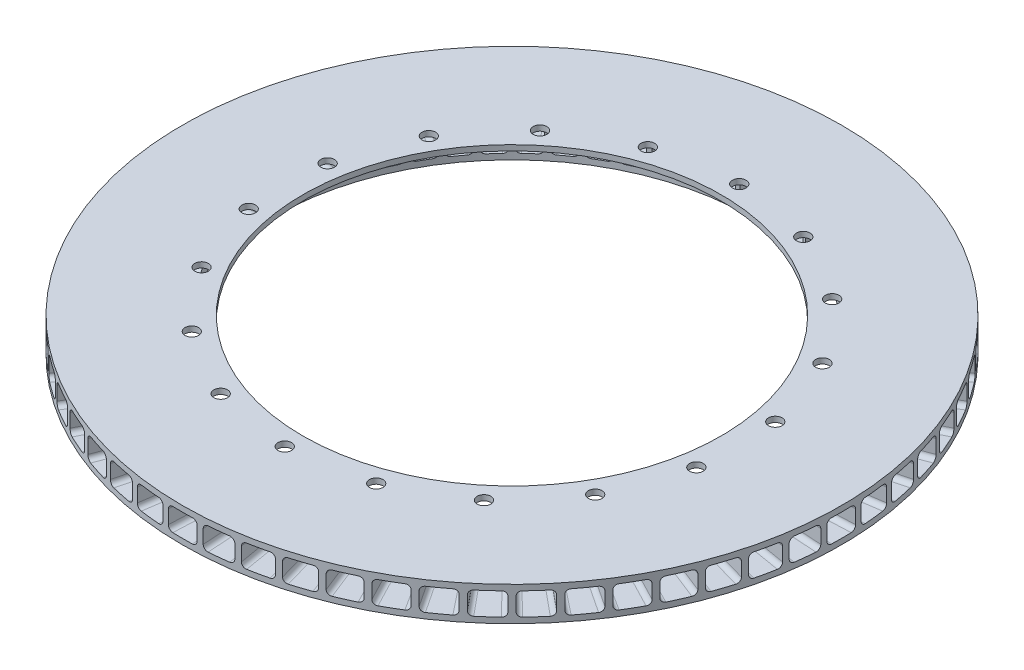
SolidWorks part; units mm, degrees
ref_plane "Front Plane" through (0, 0, 0) normal (0, 0, 1) x (1, 0, 0)
ref_plane "Top Plane" through (0, 0, 0) normal (0, 1, 0) x (1, 0, 0)
ref_plane "Right Plane" through (0, 0, 0) normal (1, 0, 0) x (0, 0, -1)
sketch "Sketch1" plane through (0, 0, 0) normal (0, 1, 0) x (1, 0, 0)
  circle A0 centre (0, 0) radius 145
  dimension "D1" = 290
extrude "Boss-Extrude1" add sketch "Sketch1" along normal mid plane 15
sketch "Sketch2" plane through (0, 7.5, 0) normal (0, 1, 0) x (1, 0, 0)
  circle A0 centre (0, 0) radius 105
  dimension "D1" = 210
extrude "Cut-Extrude1" cut sketch "Sketch2" against normal up to next
sketch "Sketch3" plane through (0, 0, 0) normal (1, 0, 0) x (0, 0, -1)
  line L0 (159.5, 0) -> (-159.5, 0) construction
  line L1 (-149, 5) -> (-104, 5)
  line L2 (-149, 5) -> (-149, -5)
  line L3 (-149, -5) -> (-104, -5)
  line L4 (-104, 5) -> (-104, -5)
  line L5 (-149, 5) -> (-104, -5) construction
  line L6 (-149, -5) -> (-104, 5) construction
  line L7 (0, 40.2612) -> (0, -51.2505) construction
  point P0 (-126.5, 0)
  dimension "D1" = 45
  dimension "D2" = 10
  dimension "D3" = 104
revolve "Cut-Revolve1" cut sketch "Sketch3" angle 5 mid plane about L7
pattern_circular "CirPattern1" count 60 over 360 about axis through (0, 7.5, 0) along (0, 1, 0) of "Cut-Revolve1"
fillet "Fillet2" radius 2 240 edges at (-18.4762, 5, 123.627) (-7.6311, 5, 124.7668) (-7.6311, -5, 124.7668) (-18.4762, -5, 123.627) (-43.7759, 5, 117.084) (-33.4048, 5, 120.4538) (-33.4048, -5, 120.4538) (-43.7759, -5, 117.084) (-67.1625, 5, 105.4239) (-57.7186, 5, 110.8764) (-57.7186, -5, 110.8764) (-67.1625, -5, 105.4239) (-87.6137, 5, 89.1563) (-79.5098, 5, 96.4531) (-79.5098, -5, 96.4531) (-87.6137, -5, 89.1563) (-97.826, -5, 77.8143) (-104.2357, -5, 68.9921) (-116.3022, 5, 45.8127) (-111.8668, 5, 55.7747) (-111.8668, -5, 55.7747) (-116.3022, -5, 45.8127) (-123.2857, 5, 20.631) (-121.0185, 5, 31.2975) (-121.0185, -5, 31.2975) (-123.2857, -5, 20.631) (-124.881, 5, -5.4524) (-124.881, 5, 5.4524) (-124.881, -5, 5.4524) (-124.881, -5, -5.4524) (-121.0185, 5, -31.2975) (-123.2857, 5, -20.631) (-123.2857, -5, -20.631) (-121.0185, -5, -31.2975) (-111.8668, 5, -55.7747) (-116.3022, 5, -45.8127) (-116.3022, -5, -45.8127) (-111.8668, -5, -55.7747) (-97.826, 5, -77.8143) (-104.2357, 5, -68.9921) (-104.2357, -5, -68.9921) (-97.826, -5, -77.8143) (-79.5098, 5, -96.4531) (-87.6137, 5, -89.1563) (-87.6137, -5, -89.1563) (-79.5098, -5, -96.4531) (-57.7186, 5, -110.8764) (-67.1625, 5, -105.4239) (-67.1625, -5, -105.4239) (-57.7186, -5, -110.8764) (-33.4048, 5, -120.4538) (-43.7759, 5, -117.084) (-43.7759, -5, -117.084) (-33.4048, -5, -120.4538) (-7.6311, 5, -124.7668) (-18.4762, 5, -123.627) (-18.4762, -5, -123.627) (-7.6311, -5, -124.7668) (18.4762, 5, -123.627) (7.6311, 5, -124.7668) (7.6311, -5, -124.7668) (18.4762, -5, -123.627) (43.7759, 5, -117.084) (33.4048, 5, -120.4538) (33.4048, -5, -120.4538) (43.7759, -5, -117.084) (67.1625, 5, -105.4239) (57.7186, 5, -110.8764) (57.7186, -5, -110.8764) (67.1625, -5, -105.4239) (87.6137, 5, -89.1563) (79.5098, 5, -96.4531) (79.5098, -5, -96.4531) (87.6137, -5, -89.1563) (104.2357, 5, -68.9921) (97.826, 5, -77.8143) (97.826, -5, -77.8143) (104.2357, -5, -68.9921) (116.3022, 5, -45.8127) (111.8668, 5, -55.7747) (111.8668, -5, -55.7747) (116.3022, -5, -45.8127) (123.2857, 5, -20.631) (121.0185, 5, -31.2975) (121.0185, -5, -31.2975) (123.2857, -5, -20.631) (124.881, 5, 5.4524) (124.881, 5, -5.4524) (124.881, -5, -5.4524) (124.881, -5, 5.4524) (121.0185, 5, 31.2975) (123.2857, 5, 20.631) (123.2857, -5, 20.631) (121.0185, -5, 31.2975) (111.8668, 5, 55.7747) (116.3022, 5, 45.8127) (116.3022, -5, 45.8127) (111.8668, -5, 55.7747) (97.826, 5, 77.8143) (104.2357, 5, 68.9921) (104.2357, -5, 68.9921) (97.826, -5, 77.8143) (79.5098, 5, 96.4531) (87.6137, 5, 89.1563) (87.6137, -5, 89.1563) (79.5098, -5, 96.4531) (57.7186, 5, 110.8764) (67.1625, 5, 105.4239) (67.1625, -5, 105.4239) (57.7186, -5, 110.8764) (33.4048, 5, 120.4538) (43.7759, 5, 117.084) (43.7759, -5, 117.084) (33.4048, -5, 120.4538) (7.6311, 5, 124.7668) (18.4762, 5, 123.627) (18.4762, -5, 123.627) (7.6311, -5, 124.7668) (-5.4524, 5, 124.881) (5.4524, 5, 124.881) (5.4524, -5, 124.881) (-5.4524, -5, 124.881) (20.631, 5, 123.2857) (31.2975, 5, 121.0185) (31.2975, -5, 121.0185) (20.631, -5, 123.2857) (45.8127, 5, 116.3022) (55.7747, 5, 111.8668) (55.7747, -5, 111.8668) (45.8127, -5, 116.3022) (68.9921, 5, 104.2357) (77.8143, 5, 97.826) (77.8143, -5, 97.826) (68.9921, -5, 104.2357) (89.1563, 5, 87.6137) (96.4531, 5, 79.5098) (96.4531, -5, 79.5098) (89.1563, -5, 87.6137) (105.4239, 5, 67.1625) (110.8764, 5, 57.7186) (110.8764, -5, 57.7186) (105.4239, -5, 67.1625) (117.084, 5, 43.7759) (120.4538, 5, 33.4048) (120.4538, -5, 33.4048) (117.084, -5, 43.7759) (123.627, 5, 18.4762) (124.7668, 5, 7.6311) (124.7668, -5, 7.6311) (123.627, -5, 18.4762) (124.7668, 5, -7.6311) (123.627, 5, -18.4762) (123.627, -5, -18.4762) (124.7668, -5, -7.6311) (120.4538, 5, -33.4048) (117.084, 5, -43.7759) (117.084, -5, -43.7759) (120.4538, -5, -33.4048) (110.8764, 5, -57.7186) (105.4239, 5, -67.1625) (105.4239, -5, -67.1625) (110.8764, -5, -57.7186) (96.4531, 5, -79.5098) (89.1563, 5, -87.6137) (89.1563, -5, -87.6137) (96.4531, -5, -79.5098) (77.8143, 5, -97.826) (68.9921, 5, -104.2357) (68.9921, -5, -104.2357) (77.8143, -5, -97.826) (55.7747, 5, -111.8668) (45.8127, 5, -116.3022) (45.8127, -5, -116.3022) (55.7747, -5, -111.8668) (31.2975, 5, -121.0185) (20.631, 5, -123.2857) (20.631, -5, -123.2857) (31.2975, -5, -121.0185) (5.4524, 5, -124.881) (-5.4524, 5, -124.881) (-5.4524, -5, -124.881) (5.4524, -5, -124.881) (-20.631, 5, -123.2857) (-31.2975, 5, -121.0185) (-31.2975, -5, -121.0185) (-20.631, -5, -123.2857) (-45.8127, 5, -116.3022) (-55.7747, 5, -111.8668) (-55.7747, -5, -111.8668) (-45.8127, -5, -116.3022) (-68.9921, 5, -104.2357) (-77.8143, 5, -97.826) (-77.8143, -5, -97.826) (-68.9921, -5, -104.2357) (-89.1563, 5, -87.6137) (-96.4531, 5, -79.5098) (-96.4531, -5, -79.5098) (-89.1563, -5, -87.6137) (-105.4239, 5, -67.1625) (-110.8764, 5, -57.7186) (-110.8764, -5, -57.7186) (-105.4239, -5, -67.1625) (-117.084, 5, -43.7759) (-120.4538, 5, -33.4048) (-120.4538, -5, -33.4048) (-117.084, -5, -43.7759) (-123.627, 5, -18.4762) (-124.7668, 5, -7.6311) (-124.7668, -5, -7.6311) (-123.627, -5, -18.4762) (-124.7668, 5, 7.6311) (-123.627, 5, 18.4762) (-123.627, -5, 18.4762) (-124.7668, -5, 7.6311) (-120.4538, 5, 33.4048) (-117.084, 5, 43.7759) (-117.084, -5, 43.7759) (-120.4538, -5, 33.4048) (-110.8764, 5, 57.7186) (-105.4239, 5, 67.1625) (-105.4239, -5, 67.1625) (-110.8764, -5, 57.7186) (-96.4531, 5, 79.5098) (-89.1563, 5, 87.6137) (-89.1563, -5, 87.6137) (-96.4531, -5, 79.5098) (-77.8143, 5, 97.826) (-68.9921, 5, 104.2357) (-68.9921, -5, 104.2357) (-77.8143, -5, 97.826) (-55.7747, 5, 111.8668) (-45.8127, 5, 116.3022) (-45.8127, -5, 116.3022) (-55.7747, -5, 111.8668) (-31.2975, 5, 121.0185) (-20.631, 5, 123.2857) (-20.631, -5, 123.2857) (-31.2975, -5, 121.0185) (-97.826, 5, 77.8143) (-104.2357, 5, 68.9921)
ref_plane "Plane1" through (0, 7.5, 0) normal (0, 1, 0) x (1, 0, 0)
sketch "Sketch6" plane through (0, 7.5, 0) normal (0, 1, 0) x (1, 0, 0)
  circle A0 centre (0, 0) radius 105
  circle A1 centre (0, 0) radius 92
  dimension "D1" = 184
extrude "Boss-Extrude2" add sketch "Sketch6" against normal blind 2.4
sketch "Sketch7" plane through (0, 7.5, 0) normal (0, 1, 0) x (1, 0, 0)
  line L0 (0, 183.5321) -> (0, -219.5809) construction
  line L1 (178.1523, 0) -> (-182.2458, 0) construction
  circle A0 centre (0, 0) radius 100 construction
  circle A1 centre (0, 100) radius 3
  dimension "D1" = 200
  dimension "D2" = 6
extrude "Cut-Extrude2" cut sketch "Sketch7" against normal up to next
pattern_circular "CirPattern2" count 18 over 360 about axis through (0, 5.1, 0) along (0, 1, 0) of "Cut-Extrude2"
